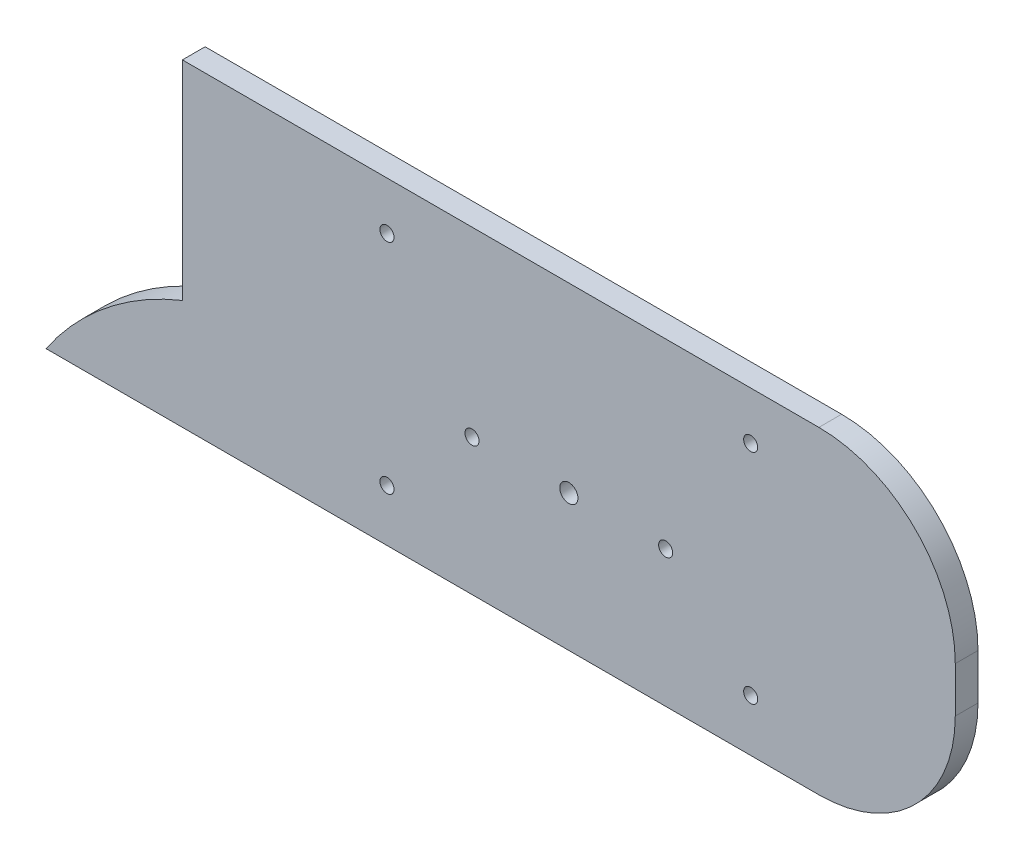
SolidWorks part; units mm, degrees
material "1060 Alloy"
ref_plane "Front Plane" through (0, 0, 0) normal (0, 0, 1) x (1, 0, 0)
ref_plane "Top Plane" through (0, 0, 0) normal (0, 1, 0) x (1, 0, 0)
ref_plane "Right Plane" through (0, 0, 0) normal (1, 0, 0) x (0, 0, -1)
sketch "Sketch2" plane through (0, 0, 0) normal (0, 0, 1) x (1, 0, 0)
  line L0 (0, 0) -> (431.8, 0)
  line L1 (76.2, 0) -> (76.2, 142.4009) construction
  line L2 (152.4, 0) -> (152.4, 186.487) construction
  line L9 (431.8, 177.8) -> (152.4, 177.8)
  line L14 (508, 76.2) -> (508, 101.6)
  line L15 (152.4, 177.8) -> (76.2, 177.8)
  line L16 (76.2, 177.8) -> (76.2, 61.4013)
  arc A5 (0, 0) -> (76.2, 61.4013) centre (138.3869, -93.7571) cw
  arc A6 (431.8, 0) -> (508, 76.2) centre (431.8, 76.2) ccw
  arc A7 (508, 101.6) -> (431.8, 177.8) centre (431.8, 101.6) ccw
  dimension "D6" = 167.1566
  dimension "D7" = 142.4009
  dimension "D5" = 177.8
  dimension "D1" = 76.2
  dimension "D4" = 431.8
  dimension "D9" = 138.3869
  dimension "D2" = 76.2
  dimension "D3" = 152.4
  dimension "D8" = 186.487
extrude "Boss-Extrude1" add sketch "Sketch2" along normal blind 12.7
sketch "Sketch3" plane through (0, 0, 0) normal (0, 0, -1) x (-1, 0, 0)
  line L0 (-76.2, 189.7623) -> (-76.2, -31.0498) construction
  line L1 (-76.2, 29.0821) -> (-494.3071, 29.0821) construction
  line L2 (-431.8, 0) -> (-433.2183, 177.7868) construction
  line L3 (0, 0) -> (-431.8, 0) construction
  arc A0 (-431.8, 177.8) -> (-508, 101.6) centre (-431.8, 101.6) ccw construction
  circle A1 centre (-190.5, 29.0821) radius 3.937
  circle A4 centre (-393.7, 29.0821) radius 3.937
  circle A7 centre (-393.7, 151.0021) radius 3.937
  circle A8 centre (-190.5, 151.0021) radius 3.937
  circle A9 centre (-325.9667, 29.0821) radius 3.937 [skipped]
  circle A10 centre (-258.2333, 29.0821) radius 3.937 [skipped]
  circle A11 centre (-325.9667, 151.0021) radius 3.937 [skipped]
  circle A12 centre (-258.2333, 151.0021) radius 3.937 [skipped]
  dimension "D5" = 7.874
  dimension "D10" = 114.3
  dimension "D1" = 76.2
  dimension "D2" = 177.7868
  dimension "D3" = 29.0821
  dimension "D4" = 114.3
  dimension "D8" = 317.5
  dimension "D9" = 121.92
  dimension "D6" = 4
  dimension "D7" = 2
extrude "Cut-Extrude1" cut sketch "Sketch3" against normal through all
sketch "Sketch4" plane through (0, 0, 12.7) normal (0, 0, 1) x (1, 0, 0)
  line L0 (292.1, 0) -> (292.1, 177.8) construction
  line L1 (0, 0) -> (431.8, 0) construction
  line L2 (431.8, 177.8) -> (76.2, 177.8) construction
  line L3 (76.2, 76.2) -> (508, 76.2) construction
  line L5 (76.2, 177.8) -> (76.2, 61.4013) construction
  circle A0 centre (292.1, 76.2) radius 5.08
  circle A1 centre (237.998, 76.2) radius 3.937
  circle A2 centre (346.202, 76.2) radius 3.937
  dimension "D1" = 10.16
  dimension "D4" = 7.874
  dimension "D5" = 7.874
  dimension "D6" = 54.102
  dimension "D7" = 54.102
  dimension "D2" = 292.1
  dimension "D3" = 76.2
extrude "Cut-Extrude2" cut sketch "Sketch4" against normal through all
equation "\"0.5n\"=0.25"
equation "\".5n\"=0.25"
